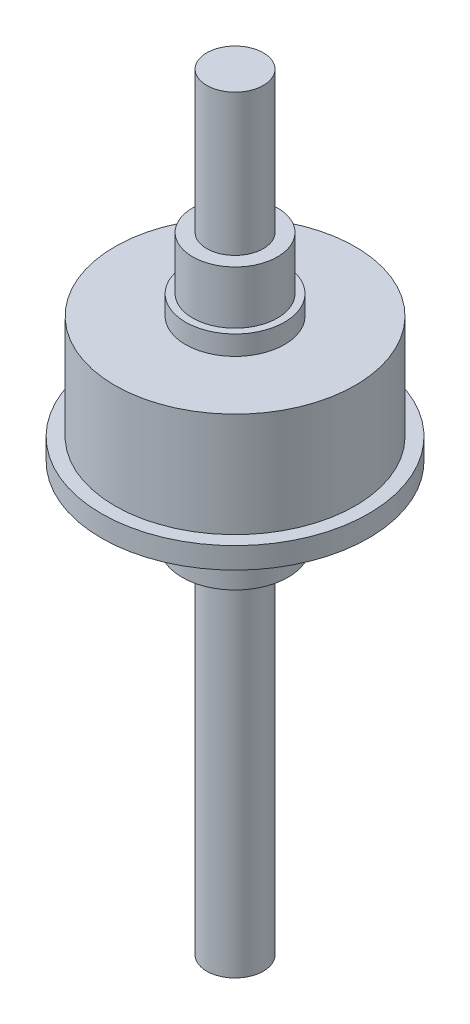
SolidWorks part; units mm, degrees
material "AISI 1035 Steel (SS)"
ref_plane "Front Plane" through (0, 0, 0) normal (0, 0, 1) x (1, 0, 0)
ref_plane "Top Plane" through (0, 0, 0) normal (0, 1, 0) x (1, 0, 0)
ref_plane "Right Plane" through (0, 0, 0) normal (1, 0, 0) x (0, 0, -1)
sketch "Sketch2" plane through (0, 0, 0) normal (0, 0, 1) x (1, 0, 0)
  line L0 (0, 40.0334) -> (0, -27.2464) construction
  line L11 (0, 0) -> (-4, 0)
  line L12 (-4, 0) -> (-4, -20)
  line L13 (-4, -20) -> (-6, -20)
  line L14 (-6, -20) -> (-6, -27.5)
  line L15 (-6, -27.5) -> (-7, -27.5)
  line L16 (-7, -27.5) -> (-7, -30.25)
  line L17 (-7, -30.25) -> (-17, -30.25)
  line L18 (-17, -30.25) -> (-17, -45.01)
  line L26 (0, -108.51) -> (0, 0)
  line L28 (-18.9, -48.01) -> (-18.9, -45.01)
  line L29 (-18.9, -45.01) -> (-17, -45.01)
  line L30 (-18.9, -48.01) -> (-9, -48.01)
  line L31 (-9, -48.01) -> (-9, -50.51)
  line L32 (-17, -45.01) -> (-17, -48.01) construction
  line L33 (-9, -50.51) -> (-7.5, -50.51)
  line L34 (-7.5, -50.51) -> (-7.5, -58.51)
  line L35 (-7.5, -58.51) -> (-4, -58.51)
  line L36 (-4, -58.51) -> (-4, -108.51)
  line L37 (-4, -108.51) -> (0, -108.51)
  dimension "D1" = 4
  dimension "D2" = 20
  dimension "D3" = 6
  dimension "D4" = 7.5
  dimension "D5" = 7
  dimension "D6" = 2.75
  dimension "D7" = 17
  dimension "D8" = 14.76
  dimension "D10" = 3
  dimension "D11" = 9
  dimension "D12" = 2.5
  dimension "D13" = 7.5
  dimension "D14" = 8
  dimension "D15" = 4
  dimension "D16" = 50
  dimension "D9" = 1.9
revolve "Revolve1" add sketch "Sketch2" angle 360 about L0
equation "\"Stator_OD\"= 68'No Tolerance given"
equation "\"A\"=18.34 'taken off spec sheet for 06808 (A)"
equation "\"Rotor_ID\"= 34'No Tolerance Given"
equation "\"back_bearing_Thickness\"= 8'randomish, thinnest off mcmaster"
equation "\"back_bearing_OD\"= 25'currently non-sense"
equation "\"Stator_Gap\"= 0.0375'+- 0.0125 (From 1.3.3.1 Kollmorgen manual)"
equation "\"Back_mount_hole\"= 1.75'To be tapped to M2 (USE LOCKTITE)"
equation "\"facePlate_Mount_Hole\"= 5.75'To be tapped to M6"
equation "\"final_shaftD\"= 8'NEMA 23 shaft diameter. Should fit with harmonic?"
equation "\"back_bearing_ID\"= 15'Random number"
equation "\"rotor_shaftD\"= \"Rotor_ID\" - (0.0185)*2'+-0.0065 (from manual)"
equation "\"back_bearing_IDOD\"= 18'Random number, OD of the inner bearing ring"
equation "\"final_shaftL\"= 50'random length. Idk"
equation "\"D1@Sketch2\" = \"final_shaftD\" / 2"
equation "\"D3@Sketch2\"=\"front_bearing_ID\"/2"
equation "\"D4@Sketch2\" = \"front_bearing_Thickness\" + 2.5"
equation "\"D5@Sketch2\"=\"front_bearing_IDOD\" / 2"
equation "\"D8@Sketch2\"=\"rotor_height\""
equation "\"front_bearing_ID\"= 12'random"
equation "\"front_bearing_OD\"= 20'random"
equation "\"front_bearing_IDOD\"= 14'random"
equation "\"front_bearing_Thickness\"= 5'randomish, thinnest off mcmaster"
equation "\"rotor_thickness\"= 2.4'measured off CAD"
equation "\"rotor_height\"= 14.76'+-0.08 taken off spec sheet for 06808 (C)"
equation "\"D11@Sketch2\"=\"back_bearing_IDOD\"/2"
equation "\"D13@Sketch2\"=\"back_bearing_ID\"/2"
equation "\"D14@Sketch2\"=\"back_bearing_Thickness\""
equation "\"D15@Sketch2\"=\"final_shaftD\"/2"
equation "\"D16@Sketch2\"=\"final_shaftL\""
equation "\"D9@Sketch2\"=\"rotor_thickness\"-0.5"
